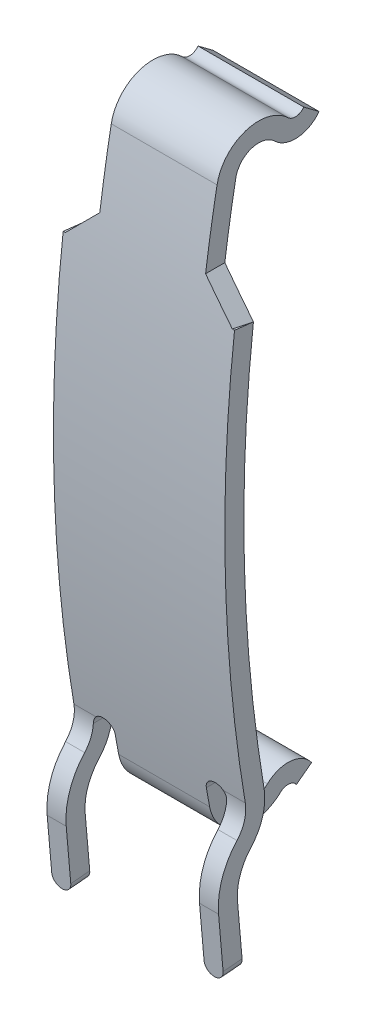
SolidWorks part; units mm, degrees
ref_plane "Front Plane" through (0, 0, 0) normal (0, 0, 1) x (1, 0, 0)
ref_plane "Top Plane" through (0, 0, 0) normal (0, 1, 0) x (1, 0, 0)
ref_plane "Right Plane" through (0, 0, 0) normal (1, 0, 0) x (0, 0, -1)
sketch "Sketch1" plane through (0, 0, 0) normal (1, 0, 0) x (0, 0, -1)
  line L0 (0, 14.45) -> (6.465, 14.45)
  line L1 (0, -14.45) -> (6.465, -14.45)
  line L2 (68.4923, 0) -> (-39.18, 0) construction
  line L3 (6.465, 12.85) -> (-0.3181, 12.85) construction
  line L4 (6.465, -12.85) -> (-0.3181, -12.85) construction
  line L5 (-3.8447, -18.35) -> (7.9378, -18.35) construction
  arc A0 (0, 14.45) -> (0, -14.45) centre (68.4923, 0) ccw
  dimension "D1" = 70
  dimension "D2" = 28.9
  dimension "D3" = 25.7
  dimension "D4" = 5.5
sketch "Sketch2" plane through (0, 0, 0) normal (1, 0, 0) x (0, 0, -1)
  line L0 (0, -14.45) -> (6.465, -14.45) construction
  line L1 (0, 14.45) -> (6.465, 14.45) construction
  line L6 (6.465, -13.75) -> (-0.3181, -13.75)
  line L7 (6.465, -13.75) -> (-0.3181, -13.75) construction
  line L9 (6.465, 13.75) -> (-0.3181, 13.75)
  line L10 (6.465, 13.75) -> (-0.3181, 13.75) construction
  arc A0 (0, 14.45) -> (0, -14.45) centre (68.4923, 0) ccw construction
  arc A1 (-0.3244, 12.8162) -> (-0.3244, -12.8162) centre (68.4923, 0) ccw
  arc A2 (-0.3244, 12.8162) -> (3.0297, 13.89) centre (1.6418, 12.45) cw
  arc A3 (3.0297, 13.89) -> (3.7767, 13.95) centre (3.3767, 14.25) ccw
  arc A4 (-0.3244, -12.8162) -> (3.0297, -13.89) centre (1.6418, -12.45) ccw
  arc A5 (3.0297, -13.89) -> (3.7767, -13.95) centre (3.3767, -14.25) cw
  dimension "D3" = 2
  dimension "D4" = 0.5
  dimension "D5" = 0.2
  dimension "D1" = 0.9
  dimension "D2" = 0.9
extrude "Extrude-Thin1" add sketch "Sketch2" along normal mid plane 8.1 thin thin type one direction reverse wall 0.9
sketch "Sketch3" plane through (0, 0, 0) normal (0, 0, 1) x (1, 0, 0)
  line L0 (-5.5, 15.45) -> (-5.5, 6.45)
  line L1 (-5.5, 6.45) -> (-2.5, 9.45)
  line L2 (-2.5, 9.45) -> (-2.5, 15.45)
  line L3 (-2.5, 15.45) -> (-5.5, 15.45)
  line L4 (2.5, 15.45) -> (2.5, 9.45)
  line L5 (2.5, 9.45) -> (5.5, 6.45)
  line L6 (5.5, 6.45) -> (5.5, 15.45)
  line L7 (5.5, 15.45) -> (2.5, 15.45)
  line L8 (0, 0) -> (0, 20.4567) construction
  line L9 (4.05, 14.45) -> (-4.05, 14.45) construction
  line L10 (-4.05, -14.45) -> (4.05, -14.45) construction
  line L11 (-5.5, -11.45) -> (-2.15, -11.45)
  line L12 (-5.5, -11.45) -> (-5.5, -16.45)
  line L13 (-5.5, -16.45) -> (-2.15, -16.45)
  line L14 (-2.15, -11.45) -> (-2.15, -16.45)
  line L15 (5.5, -11.45) -> (2.15, -11.45)
  line L16 (5.5, -11.45) -> (5.5, -16.45)
  line L17 (5.5, -16.45) -> (2.15, -16.45)
  line L18 (2.15, -11.45) -> (2.15, -16.45)
  line L19 (-4.05, 12.8162) -> (-4.05, -12.8162) construction
  dimension "D1" = 5
  dimension "D2" = 1
  dimension "D3" = 3
  dimension "D4" = 45
  dimension "D5" = 5
  dimension "D6" = 3
  dimension "D7" = 5
  dimension "D8" = 1.9
extrude "Extrude1" cut sketch "Sketch3" against normal through all and the other way through all
sketch "Sketch4" plane through (4.05, 0, 0) normal (1, 0, 0) x (0, 0, -1)
  line L0 (-0.9067, -15.4434) -> (-0.6524, -18.35)
  line L1 (-3.8447, -18.35) -> (7.9378, -18.35) construction
  line L2 (-0.6524, -18.35) -> (-0.6524, -12.0561) construction
  arc A0 (-0.1546, 7.9) -> (0.3476, -11.45) centre (68.4923, 0) ccw construction
  arc A1 (-0.1546, 7.9) -> (0.3476, -11.45) centre (68.4923, 0) ccw
  arc A2 (0.3476, -11.45) -> (-0.2671, -13.5449) centre (-2.1179, -11.8643) cw
  arc A3 (-0.2671, -13.5449) -> (-0.9067, -15.4434) centre (1.5838, -15.2255) ccw
  dimension "D2" = 2.5
  dimension "D4" = 2.5
  dimension "D1" = 5
  dimension "D3" = 1
extrude "Extrude-Thin2" add sketch "Sketch4" against normal blind 0.9 thin thin type one direction wall 0.9
mirror "Mirror2" about plane through (0, 0, 0) normal (1, 0, 0) of "Extrude-Thin2"
fillet "Fillet1" radius 0.5 4 edges at (2.15, -11.45, 0.1087) (3.15, -11.45, 0.1087) (-3.15, -11.45, 0.1087) (-2.15, -11.45, 0.1087)
fillet "Fillet2" radius 0.45 4 edges at (-4.05, -18.3892, 1.1007) (-3.15, -18.3892, 1.1007) (3.15, -18.3892, 1.1007) (4.05, -18.3892, 1.1007)
